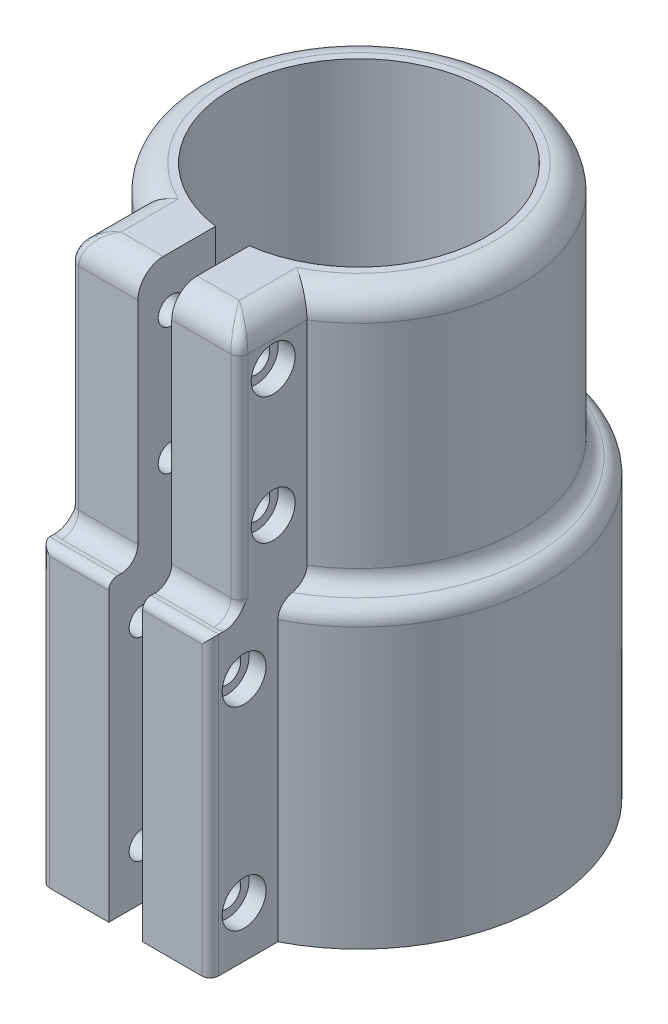
SolidWorks part; units mm, degrees
ref_plane "Front Plane" through (0, 0, 0) normal (0, 0, 1) x (1, 0, 0)
ref_plane "Top Plane" through (0, 0, 0) normal (0, 1, 0) x (1, 0, 0)
ref_plane "Right Plane" through (0, 0, 0) normal (1, 0, 0) x (0, 0, -1)
sketch "Sketch1" plane through (0, 0, 0) normal (0, 1, 0) x (1, 0, 0)
  circle A0 centre (0, 0) radius 22
  dimension "D1" = 44
extrude "Boss-Extrude1" add sketch "Sketch1" along normal blind 35
sketch "Sketch2" plane through (0, 35, 0) normal (0, 1, 0) x (1, 0, 0)
  circle A0 centre (0, 0) radius 19
  dimension "D1" = 38
extrude "Boss-Extrude2" add sketch "Sketch2" along normal blind 30
sketch "Sketch3" plane through (0, 0, 0) normal (0, -1, 0) x (1, 0, 0)
  circle A0 centre (0, 0) radius 17.6
  dimension "D1" = 35.2
extrude "Cut-Extrude1" cut sketch "Sketch3" against normal blind 30
sketch "Sketch4" plane through (0, 65, 0) normal (0, 1, 0) x (1, 0, 0)
  circle A0 centre (0, 0) radius 15.1
  dimension "D1" = 30.2
extrude "Cut-Extrude2" cut sketch "Sketch4" against normal up to next
sketch "Sketch5" plane through (0, 0, 0) normal (0, -1, 0) x (-1, 0, 0)
  line L1 (10, -27.5959) -> (-10, -27.5959)
  line L2 (10, -27.5959) -> (10, -19.5959)
  line L4 (-10, -27.5959) -> (-10, -19.5959)
  arc A2 (-10, -19.5959) -> (10, -19.5959) centre (0, 0) ccw
  dimension "D5" = 22
  dimension "D1" = 20
  dimension "D2" = 10
  dimension "D4" = 8
extrude "Boss-Extrude3" add sketch "Sketch5" against normal up to surface (35 mm away) up to face at (0, 35, 19)
sketch "Sketch6" plane through (0, 65, 0) normal (0, 1, 0) x (1, 0, 0)
  line L0 (10, -24.1555) -> (10, -16.1555)
  line L1 (10, -19.5959) -> (10, -27.5959) construction
  line L2 (10, -24.1555) -> (-10, -24.1555)
  line L3 (-10, -27.5959) -> (-10, -19.5959) construction
  line L4 (-10, -24.1555) -> (-10, -16.1555)
  arc A0 (-10, -16.1555) -> (10, -16.1555) centre (0, 0) ccw
  dimension "D2" = 19
  dimension "D1" = 8
extrude "Boss-Extrude4" add sketch "Sketch6" against normal up to surface (30 mm away) up to face at (0, 35, 19)
sketch "Sketch7" plane through (0, 65, 0) normal (0, 1, 0) x (1, 0, 0)
  line L1 (2, -27.7711) -> (-2, -27.7711)
  line L2 (2, -27.7711) -> (2, -7.8656)
  line L3 (2, -7.8656) -> (-2, -7.8656)
  line L4 (-2, -27.7711) -> (-2, -7.8656)
  dimension "D1" = 4
  dimension "D2" = 2
extrude "Cut-Extrude3" cut sketch "Sketch7" against normal through all
fillet "Fillet1" radius 3 5 edges at (-6, 65, 24.1555) (6, 65, 24.1555) (-10, 65, 20.1555) (10, 65, 20.1555) (0, 65, -19)
fillet "Fillet3" radius 1 8 edges at (-9.1213, 64.1213, 23.2768) (9.1213, 64.1213, 23.2768) (6, 35, 27.5959) (-6, 35, 27.5959) (-10, 48.5, 24.1555) (-10, 17.5, 27.5959) (10, 17.5, 27.5959) (10, 48.5, 24.1555)
fillet "Fillet4" radius 2 1 edges at (0, 35, -22)
fillet "Fillet5" radius 2 4 edges at (5.5, 35, 24.1555) (-9.7071, 35, 23.8626) (9.7071, 35, 23.8626) (-5.5, 35, 24.1555)
fillet "Fillet6" radius 2 1 edges at (0, 35, -19)
sketch "Sketch8" plane through (10, 0, 0) normal (1, 0, 0) x (0, 0, -1)
  line L0 (-24.1555, 37) -> (-24.1555, 62) construction
  line L1 (-27.5959, 0) -> (-27.5959, 34) construction
  line L2 (-21.1555, 65) -> (-14.3875, 65) construction
  line L3 (-17.8955, 34.9365) -> (20.5, 34.9365) construction
  line L4 (-19.5959, 0) -> (-26.5959, 0) construction
  circle A0 centre (-23.5959, 6) radius 1.6
  circle A1 centre (-23.5959, 28.9365) radius 1.6
  circle A2 centre (-20.1555, 59) radius 1.6
  circle A3 centre (-20.1555, 44) radius 1.6
  dimension "D7" = 3.2
  dimension "D8" = 3.2
  dimension "D9" = 3.2
  dimension "D10" = 3.2
  dimension "D1" = 4
  dimension "D2" = 4
  dimension "D3" = 4
  dimension "D4" = 4
  dimension "D5" = 6
  dimension "D6" = 15
  dimension "D11" = 6
  dimension "D12" = 6
extrude "Cut-Extrude4" cut sketch "Sketch8" against normal up to surface (20 mm away) up to face at (-10, 33.5004, 21.5019)
sketch "Sketch9" plane through (10, 0, 0) normal (1, 0, 0) x (0, 0, -1)
  circle A0 centre (-20.1555, 59) radius 2.6
  circle A1 centre (-20.1555, 44) radius 2.6
  circle A2 centre (-23.5959, 28.9365) radius 2.6
  circle A3 centre (-23.5959, 6) radius 2.6
  dimension "D1" = 5.2
  dimension "D2" = 5.2
  dimension "D3" = 5.2
  dimension "D4" = 5.2
extrude "Cut-Extrude5" cut sketch "Sketch9" against normal blind 2
sketch "Sketch11" plane through (-10, 0, 0) normal (-1, 0, 0) x (0, 0, 1)
  line L1 (20.1555, 55.8246) -> (22.9055, 57.4123)
  line L2 (22.9055, 57.4123) -> (22.9055, 60.5877)
  line L3 (22.9055, 60.5877) -> (20.1555, 62.1754)
  line L4 (20.1555, 62.1754) -> (17.4055, 60.5877)
  line L5 (17.4055, 60.5877) -> (17.4055, 57.4123)
  line L6 (17.4055, 57.4123) -> (20.1555, 55.8246)
  line L7 (20.1555, 40.8246) -> (22.9055, 42.4123)
  line L8 (22.9055, 42.4123) -> (22.9055, 45.5877)
  line L9 (22.9055, 45.5877) -> (20.1555, 47.1754)
  line L10 (20.1555, 47.1754) -> (17.4055, 45.5877)
  line L11 (17.4055, 45.5877) -> (17.4055, 42.4123)
  line L12 (17.4055, 42.4123) -> (20.1555, 40.8246)
  line L13 (23.5959, 25.7611) -> (26.3459, 27.3488)
  line L14 (26.3459, 27.3488) -> (26.3459, 30.5242)
  line L15 (26.3459, 30.5242) -> (23.5959, 32.1119)
  line L16 (23.5959, 32.1119) -> (20.8459, 30.5242)
  line L17 (20.8459, 30.5242) -> (20.8459, 27.3488)
  line L18 (20.8459, 27.3488) -> (23.5959, 25.7611)
  line L19 (23.5959, 2.8246) -> (26.3459, 4.4123)
  line L20 (26.3459, 4.4123) -> (26.3459, 7.5877)
  line L21 (26.3459, 7.5877) -> (23.5959, 9.1754)
  line L22 (23.5959, 9.1754) -> (20.8459, 7.5877)
  line L23 (20.8459, 7.5877) -> (20.8459, 4.4123)
  line L24 (20.8459, 4.4123) -> (23.5959, 2.8246)
  circle A0 centre (20.1555, 59) radius 2.75 construction
  circle A1 centre (20.1555, 44) radius 2.75 construction
  circle A2 centre (23.5959, 28.9365) radius 2.75 construction
  circle A3 centre (23.5959, 6) radius 2.75 construction
  dimension "D1" = 5.5
  dimension "D2" = 5.5
  dimension "D3" = 5.5
  dimension "D4" = 5.5
extrude "Cut-Extrude7" cut sketch "Sketch11" against normal blind 3
